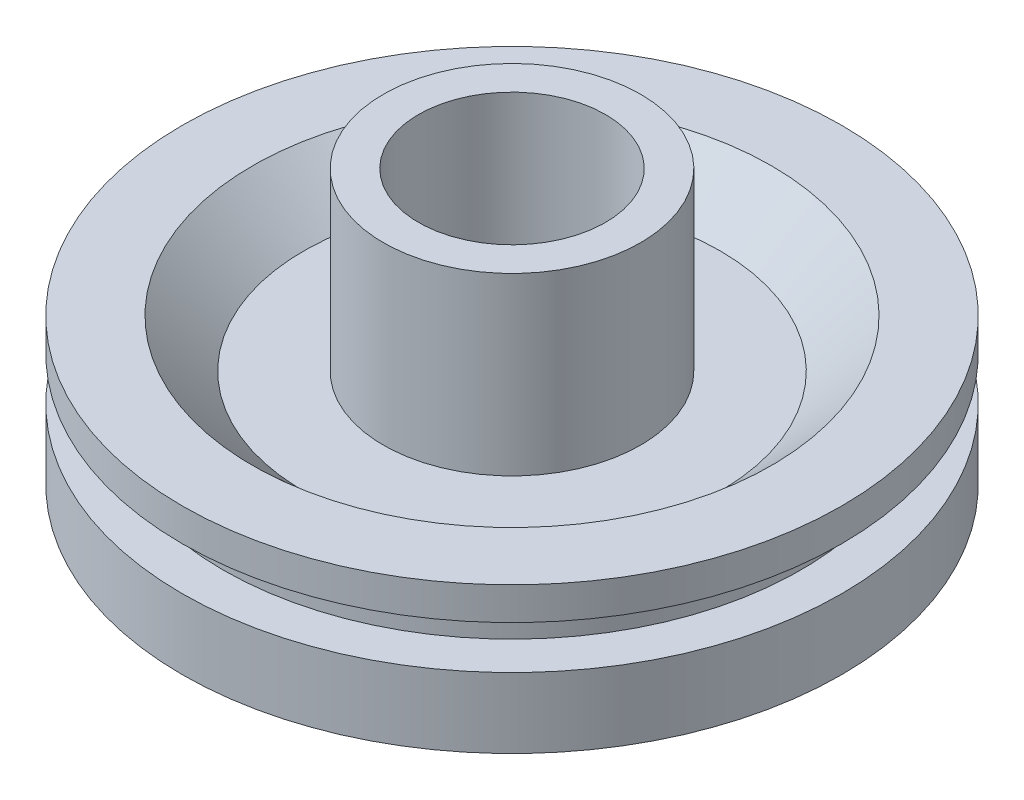
SolidWorks part; units mm, degrees
material "ABS"
ref_plane "Front Plane" through (0, 0, 0) normal (0, 0, 1) x (1, 0, 0)
ref_plane "Top Plane" through (0, 0, 0) normal (0, 1, 0) x (1, 0, 0)
ref_plane "Right Plane" through (0, 0, 0) normal (1, 0, 0) x (0, 0, -1)
sketch "Sketch1" plane through (0, 0, 0) normal (0, 0, 1) x (1, 0, 0)
  line L0 (0, 0) -> (0, 14.859) construction
  line L1 (0, 14.859) -> (5.08, 14.859) construction
  line L2 (5.08, 14.859) -> (6.985, 14.859)
  line L3 (6.985, 14.859) -> (6.985, 5.334)
  line L4 (6.985, 5.334) -> (11.303, 5.334)
  line L5 (5.08, 14.859) -> (5.08, 5.715)
  line L6 (5.08, 5.715) -> (1.524, 5.715)
  line L7 (1.524, 5.715) -> (1.524, 0)
  line L8 (1.524, 0) -> (4.8895, 0)
  line L9 (15.6845, 3.81) -> (17.907, 3.81)
  line L10 (17.907, 3.81) -> (17.907, 0)
  line L11 (16.002, 0) -> (17.907, 0)
  line L12 (15.6845, 6.1595) -> (17.907, 6.1595)
  line L13 (16.002, 0) -> (16.002, 3.04)
  line L14 (16.002, 3.04) -> (11.1989, 3.04)
  line L15 (11.1989, 3.04) -> (12.954, 0)
  line L16 (15.6845, 3.81) -> (15.6845, 6.1595)
  line L17 (17.907, 6.1595) -> (17.907, 7.9375)
  line L18 (8.9535, 0) -> (12.954, 0)
  line L19 (17.907, 7.9375) -> (14.097, 7.9375)
  line L20 (14.097, 7.9375) -> (11.303, 5.334)
  line L21 (11.303, 5.334) -> (11.303, 10.6175) construction
  line L22 (8.9535, 0) -> (8.9535, -0.889)
  line L23 (8.9535, -0.889) -> (4.8895, -0.889)
  line L24 (4.8895, -0.889) -> (4.8895, 0)
  dimension "D2" = 14.859
  dimension "D3" = 9.525
  dimension "D4" = 1.905
  dimension "D5" = 9.144
  dimension "D6" = 4.318
  dimension "D7" = 3.048
  dimension "D8" = 5.715
  dimension "D9" = 11.43
  dimension "D10" = 60
  dimension "D11" = 1.905
  dimension "D12" = 3.048
  dimension "D13" = 3.81
  dimension "D14" = 3.04
  dimension "D15" = 2.2225
  dimension "D16" = 3.81
  dimension "D17" = 1.778
  dimension "D18" = 0.889
  dimension "D19" = 4.0005
  dimension "D20" = 2.3495
  dimension "D21" = 5.08
  dimension "D22" = 4.064
  dimension "D23" = 4.8895
revolve "Revolve1" add sketch "Sketch1" angle 360 about L0
ref_plane "Plane1" through (0, -0.889, 0) normal (0, 1, 0) x (-1, 0, 0)
sketch "Sketch2" plane through (0, -0.889, 0) normal (0, 1, 0) x (-1, 0, 0)
  line L0 (1.905, 0) -> (-1.905, 0)
  line L1 (-1.905, 0) -> (-1.905, 10.2124)
  line L2 (-1.905, 10.2124) -> (1.905, 10.2124)
  line L3 (1.905, 10.2124) -> (1.905, 0)
  line L4 (0.1885, 12.6384) -> (0.813, 12.969)
  line L5 (0, 0) -> (0, 4.3661) construction
  line L6 (10.2124, 1.905) -> (10.2124, -1.905)
  line L7 (0, 1.905) -> (10.2124, 1.905)
  line L8 (10.2124, -1.905) -> (0, -1.905)
  line L9 (0, -1.905) -> (0, 1.905)
  line L10 (12.6384, -0.1885) -> (12.969, -0.813)
  line L11 (1.905, -10.2124) -> (-1.905, -10.2124)
  line L12 (1.905, 0) -> (1.905, -10.2124)
  line L13 (-1.905, -10.2124) -> (-1.905, 0)
  line L14 (-1.905, 0) -> (1.905, 0)
  line L15 (-0.1885, -12.6384) -> (-0.813, -12.969)
  line L16 (-10.2124, -1.905) -> (-10.2124, 1.905)
  line L17 (0, -1.905) -> (-10.2124, -1.905)
  line L18 (-10.2124, 1.905) -> (0, 1.905)
  line L19 (0, 1.905) -> (0, -1.905)
  line L20 (-12.6384, 0.1885) -> (-12.969, 0.813)
  arc A0 (0.813, 12.969) -> (-0.4028, 12.9882) centre (0, 0) ccw
  arc A1 (-0.4028, 12.9882) -> (0.1885, 12.6384) centre (0, 12.9944) ccw
  arc A2 (12.9882, 0.4028) -> (12.6384, -0.1885) centre (12.9944, 0) ccw
  arc A3 (12.969, -0.813) -> (12.9882, 0.4028) centre (0, 0) ccw
  arc A4 (0.4028, -12.9882) -> (-0.1885, -12.6384) centre (0, -12.9944) ccw
  arc A5 (-0.813, -12.969) -> (0.4028, -12.9882) centre (0, 0) ccw
  arc A6 (-12.9882, -0.4028) -> (-12.6384, 0.1885) centre (-12.9944, 0) ccw
  arc A7 (-12.969, 0.813) -> (-12.9882, -0.4028) centre (0, 0) ccw
  dimension "D1" = 4
extrude "Cut-Extrude1" cut sketch "Sketch2" along normal blind 0.889 contours L1 L18 L7 L3 L2 | L18 L16 L17 L13 L1 | L8 L17 L13 L11 L12 | L3 L12 L8 L6 L7 region at (-6.0587, -0.889, 0) region at (0, -0.889, 6.0587) region at (0, -0.889, -6.0587) region at (6.0587, -0.889, 0)
extrude "Cut-Extrude2" cut sketch "Sketch2<3>" along normal blind 1.778 contours L20 A7 A6 | L15 A5 A4 | L10 A3 A2 | A1 L4 A0 region at (-12.8337, -0.889, -0.0959) region at (0.0959, -0.889, -12.8337) region at (12.8337, -0.889, 0.0959)
sketch "Sketch2<3>" plane through (0, -0.889, 0) normal (0, 1, 0) x (-1, 0, 0) same geometry as "Sketch2"
